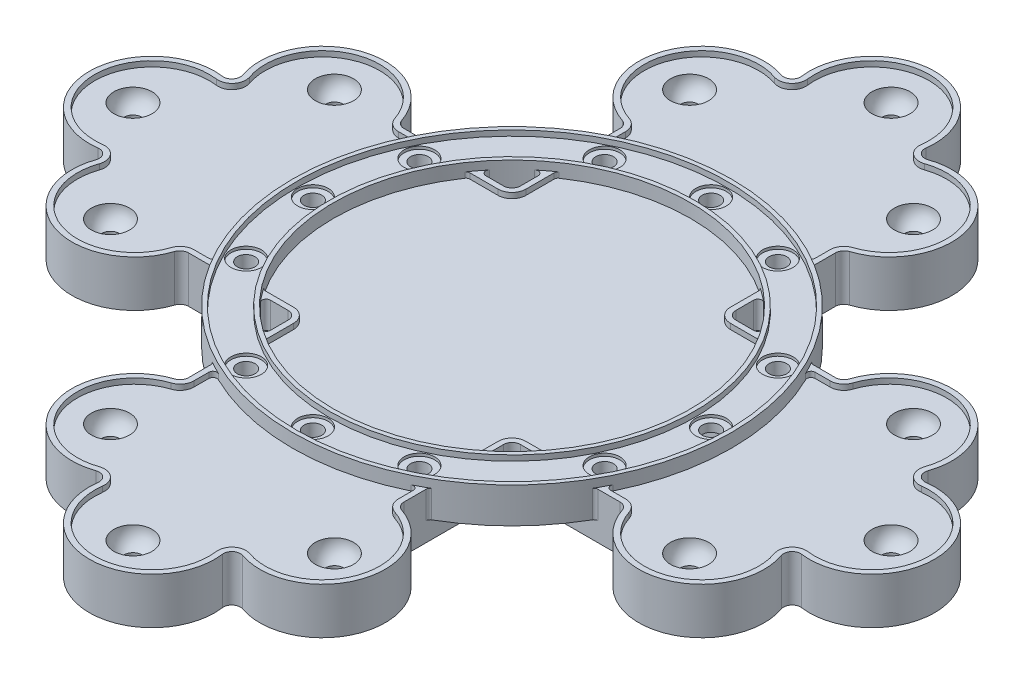
SolidWorks part; units mm, degrees
ref_plane "Front" through (0, 0, 0) normal (0, 0, 1) x (1, 0, 0)
ref_plane "Top" through (0, 0, 0) normal (0, 1, 0) x (1, 0, 0)
ref_plane "Right" through (0, 0, 0) normal (1, 0, 0) x (0, 0, -1)
sketch "Sketch1" plane through (0, 0, 0) normal (0, 1, 0) x (1, 0, 0)
  line L0 (188.3125, 0) -> (-57.7168, 0) construction
  line L1 (39.5, 42.6) -> (39.5, 79.1456)
  line L2 (-39.5, 42.6) -> (-39.5, 79.1456)
  line L3 (-42.6, 39.5) -> (-79.1456, 39.5)
  line L4 (-42.6, -39.5) -> (-79.1456, -39.5)
  line L5 (39.5, 39.5) -> (-39.5, 39.5) construction
  line L6 (0, 39.5) -> (0, 180.1734) construction
  line L7 (-39.5, 39.5) -> (-39.5, -39.5) construction
  line L8 (0, 137) -> (0, -181.6252) construction
  line L9 (-39.5, 0) -> (-180.1734, 0) construction
  line L10 (21, 122.6047) -> (-21, 122.6047) construction
  line L11 (-122.6047, 21) -> (-122.6047, -21) construction
  line L12 (-81.5, 39.5) -> (-81.5, -39.5) construction
  line L13 (39.5, 81.5) -> (-39.5, 81.5) construction
  line L14 (42.6, -39.5) -> (79.1456, -39.5)
  line L15 (42.6, 39.5) -> (79.1456, 39.5)
  line L16 (39.5, -39.5) -> (39.5, 39.5) construction
  line L17 (39.5, 0) -> (180.1734, 0) construction
  line L18 (122.6047, -21) -> (122.6047, 21) construction
  line L19 (81.5, -39.5) -> (81.5, 39.5) construction
  line L20 (-39.5, -42.6) -> (-39.5, -79.1456)
  line L21 (39.5, -42.6) -> (39.5, -79.1456)
  line L22 (-39.5, -39.5) -> (39.5, -39.5) construction
  line L23 (0, -39.5) -> (0, -180.1734) construction
  line L24 (-21, -122.6047) -> (21, -122.6047) construction
  line L25 (-39.5, -81.5) -> (39.5, -81.5) construction
  arc A0 (22.8049, 128.9962) -> (-22.8049, 128.9962) centre (0, 131.9855) ccw
  arc A1 (26.8946, 125.6645) -> (41.6299, 82.0899) centre (34.4327, 103.9349) cw
  arc A2 (-128.9962, 22.8049) -> (-128.9962, -22.8049) centre (-131.9855, 0) ccw
  arc A3 (-125.6645, 26.8946) -> (-82.0899, 41.6299) centre (-103.9349, 34.4327) cw
  arc A4 (-125.6645, -26.8946) -> (-82.0899, -41.6299) centre (-103.9349, -34.4327) ccw
  arc A5 (-26.8946, 125.6645) -> (-41.6299, 82.0899) centre (-34.4327, 103.9349) ccw
  arc A6 (128.9962, -22.8049) -> (128.9962, 22.8049) centre (131.9855, 0) ccw
  arc A7 (125.6645, -26.8946) -> (82.0899, -41.6299) centre (103.9349, -34.4327) cw
  arc A8 (125.6645, 26.8946) -> (82.0899, 41.6299) centre (103.9349, 34.4327) ccw
  arc A9 (-22.8049, -128.9962) -> (22.8049, -128.9962) centre (0, -131.9855) ccw
  arc A10 (-26.8946, -125.6645) -> (-41.6299, -82.0899) centre (-34.4327, -103.9349) cw
  arc A11 (26.8946, -125.6645) -> (41.6299, -82.0899) centre (34.4327, -103.9349) ccw
  arc A12 (-42.6, -39.5) -> (-39.5, -42.6) centre (-42.6, -42.6) cw
  arc A13 (-39.5, -79.1456) -> (-41.6299, -82.0899) centre (-42.6, -79.1456) cw
  arc A14 (-22.8049, -128.9962) -> (-26.8946, -125.6645) centre (-25.8786, -128.5933) ccw
  arc A15 (22.8049, -128.9962) -> (26.8946, -125.6645) centre (25.8786, -128.5933) cw
  arc A16 (39.5, -79.1456) -> (41.6299, -82.0899) centre (42.6, -79.1456) ccw
  arc A17 (42.6, -39.5) -> (39.5, -42.6) centre (42.6, -42.6) ccw
  arc A18 (79.1456, -39.5) -> (82.0899, -41.6299) centre (79.1456, -42.6) cw
  arc A19 (128.9962, -22.8049) -> (125.6645, -26.8946) centre (128.5933, -25.8786) ccw
  arc A20 (128.9962, 22.8049) -> (125.6645, 26.8946) centre (128.5933, 25.8786) cw
  arc A21 (79.1456, 39.5) -> (82.0899, 41.6299) centre (79.1456, 42.6) ccw
  arc A22 (39.5, 42.6) -> (42.6, 39.5) centre (42.6, 42.6) ccw
  arc A23 (39.5, 79.1456) -> (41.6299, 82.0899) centre (42.6, 79.1456) cw
  arc A24 (22.8049, 128.9962) -> (26.8946, 125.6645) centre (25.8786, 128.5933) ccw
  arc A25 (-22.8049, 128.9962) -> (-26.8946, 125.6645) centre (-25.8786, 128.5933) cw
  arc A26 (-39.5, 79.1456) -> (-41.6299, 82.0899) centre (-42.6, 79.1456) ccw
  arc A27 (-42.6, 39.5) -> (-39.5, 42.6) centre (-42.6, 42.6) ccw
  arc A28 (-79.1456, -39.5) -> (-82.0899, -41.6299) centre (-79.1456, -42.6) ccw
  arc A29 (-79.1456, 39.5) -> (-82.0899, 41.6299) centre (-79.1456, 42.6) cw
  arc A30 (-128.9962, -22.8049) -> (-125.6645, -26.8946) centre (-128.5933, -25.8786) cw
  arc A31 (-128.9962, 22.8049) -> (-125.6645, 26.8946) centre (-128.5933, 25.8786) ccw
  point P52 (0, 0)
  dimension "D7" = 3.1
  dimension "D3" = 42
  dimension "D2" = 23
  dimension "D1" = 39.5
  dimension "D4" = 79
  dimension "D5" = 4
  dimension "D6" = 42
extrude "Boss-Extrude1" add sketch "Sketch1" along normal blind 17
ref_plane "Plane1" through (0, 17, 0) normal (0, 1, 0) x (1, 0, 0)
sketch "Sketch8" plane through (0, 17, 0) normal (0, 1, 0) x (1, 0, 0)
  line L244 (42.6, -37.5) -> (79.1456, -37.5)
  line L245 (37.5, -79.1456) -> (37.5, -42.6)
  line L246 (-37.5, -42.6) -> (-37.5, -79.1456)
  line L247 (-79.1456, -37.5) -> (-42.6, -37.5)
  line L248 (79.1456, 37.5) -> (42.6, 37.5)
  line L249 (37.5, 42.6) -> (37.5, 79.1456)
  line L250 (-37.5, 79.1456) -> (-37.5, 42.6)
  line L251 (-42.6, 37.5) -> (-79.1456, 37.5)
  line L252 (42.6, -37.5) -> (79.1456, -37.5)
  line L253 (37.5, -79.1456) -> (37.5, -42.6)
  line L254 (-37.5, -42.6) -> (-37.5, -79.1456)
  line L255 (-79.1456, -37.5) -> (-42.6, -37.5)
  line L256 (79.1456, 37.5) -> (42.6, 37.5)
  line L257 (37.5, 42.6) -> (37.5, 79.1456)
  line L258 (-37.5, 79.1456) -> (-37.5, 42.6)
  line L259 (-42.6, 37.5) -> (-79.1456, 37.5)
  arc A637 (-37.5, 79.1456) -> (-41.0041, 83.9895) centre (-42.6, 79.1456) ccw
  arc A638 (-27.5501, 123.775) -> (-20.8219, 129.2561) centre (-25.8786, 128.5933) ccw
  arc A639 (20.8219, 129.2561) -> (27.5501, 123.775) centre (25.8786, 128.5933) ccw
  arc A640 (41.0041, 83.9895) -> (37.5, 79.1456) centre (42.6, 79.1456) ccw
  arc A641 (79.1456, 37.5) -> (83.9895, 41.0041) centre (79.1456, 42.6) ccw
  arc A642 (123.775, 27.5501) -> (83.9895, 41.0041) centre (103.9349, 34.4327) ccw
  arc A643 (123.775, 27.5501) -> (129.2561, 20.8219) centre (128.5933, 25.8786) ccw
  arc A644 (129.2561, -20.8219) -> (129.2561, 20.8219) centre (131.9855, 0) ccw
  arc A645 (129.2561, -20.8219) -> (123.775, -27.5501) centre (128.5933, -25.8786) ccw
  arc A646 (83.9895, -41.0041) -> (123.775, -27.5501) centre (103.9349, -34.4327) ccw
  arc A647 (83.9895, -41.0041) -> (79.1456, -37.5) centre (79.1456, -42.6) ccw
  arc A648 (42.6, -37.5) -> (37.5, -42.6) centre (42.6, -42.6) ccw
  arc A649 (37.5, -79.1456) -> (41.0041, -83.9895) centre (42.6, -79.1456) ccw
  arc A650 (27.5501, -123.775) -> (41.0041, -83.9895) centre (34.4327, -103.9349) ccw
  arc A651 (27.5501, -123.775) -> (20.8219, -129.2561) centre (25.8786, -128.5933) ccw
  arc A652 (-20.8219, -129.2561) -> (20.8219, -129.2561) centre (0, -131.9855) ccw
  arc A653 (-20.8219, -129.2561) -> (-27.5501, -123.775) centre (-25.8786, -128.5933) ccw
  arc A654 (-41.0041, -83.9895) -> (-27.5501, -123.775) centre (-34.4327, -103.9349) ccw
  arc A655 (-41.0041, -83.9895) -> (-37.5, -79.1456) centre (-42.6, -79.1456) ccw
  arc A656 (-37.5, -42.6) -> (-42.6, -37.5) centre (-42.6, -42.6) ccw
  arc A657 (-79.1456, -37.5) -> (-83.9895, -41.0041) centre (-79.1456, -42.6) ccw
  arc A658 (-123.775, -27.5501) -> (-83.9895, -41.0041) centre (-103.9349, -34.4327) ccw
  arc A659 (-123.775, -27.5501) -> (-129.2561, -20.8219) centre (-128.5933, -25.8786) ccw
  arc A660 (-129.2561, 20.8219) -> (-129.2561, -20.8219) centre (-131.9855, 0) ccw
  arc A661 (-129.2561, 20.8219) -> (-123.775, 27.5501) centre (-128.5933, 25.8786) ccw
  arc A662 (-83.9895, 41.0041) -> (-79.1456, 37.5) centre (-79.1456, 42.6) ccw
  arc A663 (-83.9895, 41.0041) -> (-123.775, 27.5501) centre (-103.9349, 34.4327) ccw
  arc A664 (37.5, 42.6) -> (42.6, 37.5) centre (42.6, 42.6) ccw
  arc A665 (-42.6, 37.5) -> (-37.5, 42.6) centre (-42.6, 42.6) ccw
  arc A666 (41.0041, 83.9895) -> (27.5501, 123.775) centre (34.4327, 103.9349) ccw
  arc A667 (20.8219, 129.2561) -> (-20.8219, 129.2561) centre (0, 131.9855) ccw
  arc A668 (-27.5501, 123.775) -> (-41.0041, 83.9895) centre (-34.4327, 103.9349) ccw
  arc A669 (-37.5, 79.1456) -> (-41.0041, 83.9895) centre (-42.6, 79.1456) ccw
  arc A670 (-27.5501, 123.775) -> (-20.8219, 129.2561) centre (-25.8786, 128.5933) ccw
  arc A671 (20.8219, 129.2561) -> (27.5501, 123.775) centre (25.8786, 128.5933) ccw
  arc A672 (41.0041, 83.9895) -> (37.5, 79.1456) centre (42.6, 79.1456) ccw
  arc A673 (79.1456, 37.5) -> (83.9895, 41.0041) centre (79.1456, 42.6) ccw
  arc A674 (123.775, 27.5501) -> (83.9895, 41.0041) centre (103.9349, 34.4327) ccw
  arc A675 (123.775, 27.5501) -> (129.2561, 20.8219) centre (128.5933, 25.8786) ccw
  arc A676 (129.2561, -20.8219) -> (129.2561, 20.8219) centre (131.9855, 0) ccw
  arc A677 (129.2561, -20.8219) -> (123.775, -27.5501) centre (128.5933, -25.8786) ccw
  arc A678 (83.9895, -41.0041) -> (123.775, -27.5501) centre (103.9349, -34.4327) ccw
  arc A679 (83.9895, -41.0041) -> (79.1456, -37.5) centre (79.1456, -42.6) ccw
  arc A680 (42.6, -37.5) -> (37.5, -42.6) centre (42.6, -42.6) ccw
  arc A681 (37.5, -79.1456) -> (41.0041, -83.9895) centre (42.6, -79.1456) ccw
  arc A682 (27.5501, -123.775) -> (41.0041, -83.9895) centre (34.4327, -103.9349) ccw
  arc A683 (27.5501, -123.775) -> (20.8219, -129.2561) centre (25.8786, -128.5933) ccw
  arc A684 (-20.8219, -129.2561) -> (20.8219, -129.2561) centre (0, -131.9855) ccw
  arc A685 (-20.8219, -129.2561) -> (-27.5501, -123.775) centre (-25.8786, -128.5933) ccw
  arc A686 (-41.0041, -83.9895) -> (-27.5501, -123.775) centre (-34.4327, -103.9349) ccw
  arc A687 (-41.0041, -83.9895) -> (-37.5, -79.1456) centre (-42.6, -79.1456) ccw
  arc A688 (-37.5, -42.6) -> (-42.6, -37.5) centre (-42.6, -42.6) ccw
  arc A689 (-79.1456, -37.5) -> (-83.9895, -41.0041) centre (-79.1456, -42.6) ccw
  arc A690 (-123.775, -27.5501) -> (-83.9895, -41.0041) centre (-103.9349, -34.4327) ccw
  arc A691 (-123.775, -27.5501) -> (-129.2561, -20.8219) centre (-128.5933, -25.8786) ccw
  arc A692 (-129.2561, 20.8219) -> (-129.2561, -20.8219) centre (-131.9855, 0) ccw
  arc A693 (-129.2561, 20.8219) -> (-123.775, 27.5501) centre (-128.5933, 25.8786) ccw
  arc A694 (-83.9895, 41.0041) -> (-79.1456, 37.5) centre (-79.1456, 42.6) ccw
  arc A695 (-83.9895, 41.0041) -> (-123.775, 27.5501) centre (-103.9349, 34.4327) ccw
  arc A696 (37.5, 42.6) -> (42.6, 37.5) centre (42.6, 42.6) ccw
  arc A697 (-42.6, 37.5) -> (-37.5, 42.6) centre (-42.6, 42.6) ccw
  arc A698 (41.0041, 83.9895) -> (27.5501, 123.775) centre (34.4327, 103.9349) ccw
  arc A699 (20.8219, 129.2561) -> (-20.8219, 129.2561) centre (0, 131.9855) ccw
  arc A700 (-27.5501, 123.775) -> (-41.0041, 83.9895) centre (-34.4327, 103.9349) ccw
  dimension "D1" = 2
extrude "Cut-Extrude1" cut sketch "Sketch8" against normal blind 2
sketch "Sketch9" plane through (0, 17, 0) normal (0, 1, 0) x (1, 0, 0)
  circle A0 centre (0, 0) radius 65.5
  circle A1 centre (0, 0) radius 80.5
  dimension "D1" = 131
  dimension "D2" = 161
extrude "Boss-Extrude3" add sketch "Sketch9" along normal blind 3 and the other way blind 10
ref_plane "Plane2" through (0, 20, 0) normal (0, 1, 0) x (1, 0, 0)
sketch "Sketch11" plane through (0, 20, 0) normal (0, 1, 0) x (1, 0, 0)
  circle A9 centre (0, 0) radius 79
  circle A10 centre (0, 0) radius 79
  circle A12 centre (0, 0) radius 67
  circle A13 centre (0, 0) radius 67
  dimension "D1" = 1.5
  dimension "D2" = 1.5
extrude "Cut-Extrude2" cut sketch "Sketch11" against normal blind 2
ref_plane "Plane3" through (0, 0, 0) normal (0, -1, 0) x (-1, 0, 0)
sketch "Sketch12" plane through (0, 0, 0) normal (0, -1, 0) x (-1, 0, 0)
  line L0 (-49.0448, 35.71) -> (-6.2448, 35.71)
  line L1 (-3.1448, 38.81) -> (-3.1448, 61.81)
  line L2 (-3.1448, 61.81) -> (18.8552, 61.81)
  line L3 (18.8552, 61.81) -> (18.8552, 38.81)
  line L4 (21.9552, 35.71) -> (45.7552, 35.71)
  line L5 (48.8552, 32.61) -> (48.8552, 0.81)
  line L6 (51.9552, -2.29) -> (74.9552, -2.29)
  line L7 (74.9552, -2.29) -> (74.9552, -25.29)
  line L8 (74.9552, -25.29) -> (51.9552, -25.29)
  line L9 (48.8552, -28.39) -> (48.8552, -33.19)
  line L10 (45.7552, -36.29) -> (24.9552, -36.29)
  line L11 (21.8552, -39.39) -> (21.8552, -62.39)
  line L12 (21.8552, -62.39) -> (-0.1448, -62.39)
  line L13 (-0.1448, -62.39) -> (-0.1448, -39.39)
  line L14 (-3.2448, -36.29) -> (-49.0448, -36.29)
  line L15 (-52.1448, -33.19) -> (-52.1448, -11.39)
  line L16 (-55.2448, -8.29) -> (-78.2448, -8.29)
  line L17 (-78.2448, -8.29) -> (-78.2448, 13.71)
  line L18 (-78.2448, 13.71) -> (-55.2448, 13.71)
  line L19 (-52.1448, 16.81) -> (-52.1448, 32.61)
  arc A0 (-6.2448, 35.71) -> (-3.1448, 38.81) centre (-6.2448, 38.81) ccw
  arc A1 (18.8552, 38.81) -> (21.9552, 35.71) centre (21.9552, 38.81) ccw
  arc A2 (45.7552, 35.71) -> (48.8552, 32.61) centre (45.7552, 32.61) cw
  arc A3 (48.8552, 0.81) -> (51.9552, -2.29) centre (51.9552, 0.81) ccw
  arc A4 (51.9552, -25.29) -> (48.8552, -28.39) centre (51.9552, -28.39) ccw
  arc A5 (48.8552, -33.19) -> (45.7552, -36.29) centre (45.7552, -33.19) cw
  arc A6 (24.9552, -36.29) -> (21.8552, -39.39) centre (24.9552, -39.39) ccw
  arc A7 (-0.1448, -39.39) -> (-3.2448, -36.29) centre (-3.2448, -39.39) ccw
  arc A8 (-49.0448, -36.29) -> (-52.1448, -33.19) centre (-49.0448, -33.19) cw
  arc A9 (-52.1448, -11.39) -> (-55.2448, -8.29) centre (-55.2448, -11.39) ccw
  arc A10 (-55.2448, 13.71) -> (-52.1448, 16.81) centre (-55.2448, 16.81) ccw
  arc A11 (-49.0448, 35.71) -> (-52.1448, 32.61) centre (-49.0448, 32.61) ccw
  point P22 (-3.1448, 35.71)
  point P25 (18.8552, 35.71)
  point P28 (48.8552, 35.71)
  point P31 (48.8552, -2.29)
  point P34 (48.8552, -25.29)
  point P37 (48.8552, -36.29)
  point P40 (21.8552, -36.29)
  point P43 (-0.1448, -36.29)
  point P46 (-52.1448, -36.29)
  point P49 (-52.1448, -8.29)
  point P52 (-52.1448, 13.71)
  point P55 (-52.1448, 35.71)
  dimension "D11" = 3.1
  dimension "D1" = 72
  dimension "D2" = 101
  dimension "D3" = 30
  dimension "D4" = 22
  dimension "D5" = 22
  dimension "D6" = 22
  dimension "D7" = 52
  dimension "D8" = 22
  dimension "D9" = 11
  dimension "D10" = 23
  dimension "D12" = 23
  dimension "D13" = 23
  dimension "D14" = 23
  dimension "D15" = 23
extrude "Cut-Extrude3" cut sketch "Sketch12" against normal blind 14
ref_plane "Plane4" through (0, 18, 0) normal (0, 1, 0) x (1, 0, 0)
sketch "Sketch13" plane through (0, 18, 0) normal (0, 1, 0) x (1, 0, 0)
  line L0 (0, 109.8367) -> (0, 39.5) construction
  line L1 (0, 39.5) -> (0, 180.1734) construction
  circle A0 centre (0, 0) radius 73 construction
  circle A1 centre (0, 73) radius 3.25
  circle A2 centre (-31.7669, 65.7257) radius 3.25
  circle A3 centre (31.7669, 65.7257) radius 3.25
  circle A4 centre (65.7257, 31.7669) radius 3.25
  circle A5 centre (73, 0) radius 3.25
  circle A6 centre (65.7257, -31.7669) radius 3.25
  circle A7 centre (31.7669, -65.7257) radius 3.25
  circle A8 centre (0, -73) radius 3.25
  circle A9 centre (-31.7669, -65.7257) radius 3.25
  circle A10 centre (-65.7257, -31.7669) radius 3.25
  circle A11 centre (-73, 0) radius 3.25
  circle A12 centre (-65.7257, 31.7669) radius 3.25
  point P35 (0, 0)
  dimension "D1" = 146
  dimension "D2" = 6.5
  dimension "D3" = 6.5
  dimension "D4" = 4
extrude "Cut-Extrude4" cut sketch "Sketch13" against normal through all
sketch "Sketch14" plane through (0, 18, 0) normal (0, 1, 0) x (1, 0, 0)
  line L0 (0, 39.5) -> (0, 180.1734) construction
  line L1 (0, 99.6735) -> (0, 45.2038) construction
  circle A0 centre (0, 0) radius 73 construction
  circle A1 centre (0, 73) radius 5.6
  circle A2 centre (-31.7669, 65.7257) radius 5.6
  circle A3 centre (31.7669, 65.7257) radius 5.6
  circle A4 centre (65.7257, 31.7669) radius 5.6
  circle A5 centre (73, 0) radius 5.6
  circle A6 centre (65.7257, -31.7669) radius 5.6
  circle A7 centre (31.7669, -65.7257) radius 5.6
  circle A8 centre (0, -73) radius 5.6
  circle A9 centre (-31.7669, -65.7257) radius 5.6
  circle A10 centre (-65.7257, -31.7669) radius 5.6
  circle A11 centre (-73, 0) radius 5.6
  circle A12 centre (-65.7257, 31.7669) radius 5.6
  point P35 (0, 0)
  dimension "D1" = 146
  dimension "D2" = 11.2
  dimension "D3" = 11.2
  dimension "D4" = 4
extrude "Cut-Extrude5" cut sketch "Sketch14" against normal blind 1
sketch "Sketch15" plane through (0, 17, 0) normal (0, 1, 0) x (1, 0, 0)
  line L0 (0, 131.9855) -> (0, 152.9855) construction
  line L2 (-34.4327, 103.9349) -> (-54.326, 110.6621) construction
  circle A0 centre (-41.0638, 106.1773) radius 7 construction
  arc A1 (-27.5501, 123.775) -> (-41.0041, 83.9895) centre (-34.4327, 103.9349) ccw construction
  circle A2 centre (-41.0638, 106.1773) radius 3.25
  arc A3 (20.8219, 129.2561) -> (-20.8219, 129.2561) centre (0, 131.9855) ccw construction
  circle A4 centre (0, 138.9855) radius 7 construction
  circle A5 centre (0, 138.9855) radius 3.25
  circle A6 centre (41.0638, 106.1773) radius 3.25
  circle A7 centre (106.1773, 41.0638) radius 3.25
  circle A8 centre (138.9855, 0) radius 3.25
  circle A9 centre (106.1773, -41.0638) radius 3.25
  circle A10 centre (41.0638, -106.1773) radius 3.25
  circle A11 centre (0, -138.9855) radius 3.25
  circle A12 centre (-41.0638, -106.1773) radius 3.25
  circle A13 centre (-106.1773, -41.0638) radius 3.25
  circle A14 centre (-138.9855, 0) radius 3.25
  circle A15 centre (-106.1773, 41.0638) radius 3.25
  point P41 (0, 0)
  dimension "D1" = 14
  dimension "D2" = 6.5
  dimension "D3" = 14
  dimension "D4" = 6.5
  dimension "D5" = 4
extrude "Cut-Extrude6" cut sketch "Sketch15" against normal through all
sketch "Sketch16" plane through (0, 0, 0) normal (1, 0, 0) x (0, 0, -1)
  line L0 (131.9855, 15) -> (138.9855, 15)
  line L1 (138.9855, 15) -> (138.9855, 8)
  line L4 (135.7355, 15) -> (142.2355, 15) construction
  line L5 (142.2355, 15) -> (135.7355, 15) construction
  line L6 (152.9855, 15) -> (129.2561, 15) construction
  arc A0 (138.9855, 8) -> (131.9855, 15) centre (138.9855, 15) cw
  dimension "D1" = 7
revolve "Cut-Revolve1" cut sketch "Sketch16" angle 360 about L1
ref_axis "Axis1" through (41.0638, 0, -106.1773) along (0, 1, 0)
ref_plane "Plane5" through (41.0638, 0, 0) normal (1, 0, 0) x (0, 0, -1)
sketch "Sketch18" plane through (41.0638, 0, 0) normal (1, 0, 0) x (0, 0, -1)
  line L0 (99.1773, 15) -> (106.1773, 15)
  line L1 (106.1773, 15) -> (106.1773, 8)
  line L3 (102.9273, 15) -> (109.4273, 15) construction
  arc A0 (99.1773, 15) -> (106.1773, 8) centre (106.1773, 15) ccw
  dimension "D1" = 7
revolve "Cut-Revolve3" cut sketch "Sketch18" angle 360 about L1
ref_axis "Axis2" through (-41.0638, 0, -106.1773) along (0, 1, 0)
mirror "Mirror1" about plane through (0, 0, 0) normal (1, 0, 0) of "Cut-Revolve3"
ref_axis "Axis3" through (0, 0, 0) along (0, 1, 0)
pattern_circular "CirPattern1" count 4 over 360 about axis through (0, 0, 0) along (0, 1, 0) of "Cut-Revolve1", "Cut-Revolve3", "Mirror1"
sketch "Sketch19" plane through (0, 0, 0) normal (0, -1, 0) x (-1, 0, 0)
  line L0 (-78.2448, 13.71) -> (-87.017, 13.71)
  line L1 (-90.117, 16.81) -> (-90.117, 25.8454)
  line L2 (-87.017, 28.9454) -> (-65.921, 28.9454)
  line L3 (-65.921, 28.9454) -> (-65.921, 32.6006)
  line L4 (-65.921, 32.6006) -> (-101.2665, 32.6006)
  line L5 (-104.3665, 35.7006) -> (-104.3665, 41.0638)
  line L6 (-104.3665, 41.0638) -> (-107.8155, 41.0638)
  line L7 (-107.8155, 41.0638) -> (-107.8155, 13.71)
  line L8 (-107.8155, 13.71) -> (-107.8155, 5.4684)
  line L9 (-110.9155, 2.3684) -> (-137.9358, 2.3684)
  line L10 (-137.9358, 2.3684) -> (-137.9358, -1.5741)
  line L11 (-137.9358, -1.5741) -> (-110.9155, -1.5741)
  line L12 (-107.8155, -4.6741) -> (-107.8155, -40.3886)
  line L13 (-107.8155, -40.3886) -> (-104.3665, -40.3886)
  line L14 (-104.3665, -40.3886) -> (-104.3665, -37.5327)
  line L15 (-101.2665, -34.4327) -> (-65.921, -34.4327)
  line L16 (-65.921, -34.4327) -> (-65.921, -29.8338)
  line L17 (-65.921, -29.8338) -> (-87.017, -29.8338)
  line L18 (-90.117, -26.7338) -> (-90.117, -11.4)
  line L19 (-87.0206, -8.3) -> (-78.2448, -8.29)
  line L20 (-78.2448, -8.29) -> (-78.2448, 13.71)
  line L22 (-3.1448, 61.81) -> (-31.7669, 62.4757)
  line L23 (-31.7669, 62.4757) -> (-31.7669, 68.9757)
  line L24 (-31.7669, 68.9757) -> (-11.0716, 68.9757)
  line L25 (-7.9716, 72.0757) -> (-7.9716, 99.676)
  line L26 (-11.0559, 102.776) -> (-41.0638, 102.9273)
  line L27 (-41.0638, 102.9273) -> (-41.0638, 109.4273)
  line L28 (-41.0638, 9.9) -> (-41.0638, -9.9) construction
  line L29 (-41.0638, 109.4273) -> (-5.8699, 109.4273)
  line L30 (-2.7699, 112.5273) -> (-2.7699, 138.9855)
  line L31 (-2.7699, 138.9855) -> (3.25, 138.9855)
  line L32 (3.25, 138.9855) -> (3.25, 112.5273)
  line L33 (6.35, 109.4273) -> (41.0638, 109.4273)
  line L34 (41.0638, 109.4273) -> (41.0638, 102.9273)
  line L35 (41.0638, 102.9273) -> (6.2493, 102.9273)
  line L36 (3.1493, 99.8273) -> (3.1493, 72.0757)
  line L37 (6.2493, 68.9757) -> (31.7669, 68.9757)
  line L38 (31.7669, 68.9757) -> (31.7669, 62.4757)
  line L39 (31.7669, 62.4757) -> (18.8552, 61.81)
  line L40 (18.8552, 61.81) -> (-3.1448, 61.81)
  line L41 (65.7257, -29.8338) -> (71.8552, -29.8338)
  line L42 (74.9552, -26.7338) -> (74.9552, -25.29)
  line L43 (-31.7669, -62.4757) -> (-0.1448, -62.4757)
  line L44 (65.7257, -29.8338) -> (65.7257, -35.0169)
  line L45 (65.7257, -35.0169) -> (100.8349, -35.0169)
  line L46 (103.9349, -38.1169) -> (103.9349, -41.0638)
  line L47 (103.9349, -41.0638) -> (109.4273, -41.0638)
  line L48 (109.4273, -41.0638) -> (109.4273, -5.6961)
  line L49 (112.5273, -2.5961) -> (139.1518, -2.5961)
  line L50 (139.1518, -2.5961) -> (138.9855, 3.25)
  line L51 (138.9855, 3.25) -> (112.5273, 3.25)
  line L52 (109.4273, 6.35) -> (109.4273, 41.0638)
  line L53 (109.4273, 41.0638) -> (102.9273, 41.0638)
  line L54 (102.9273, 41.0638) -> (102.9273, 37.6246)
  line L55 (99.8273, 34.5246) -> (65.7257, 34.5246)
  line L56 (65.7257, 34.5246) -> (65.7257, 28.9454)
  line L57 (65.7257, 28.9454) -> (83.7971, 28.9454)
  line L58 (86.8971, 25.8454) -> (86.8971, 6.2631)
  line L59 (83.8852, 3.1643) -> (74.4737, 2.8966)
  line L61 (74.4737, 2.8966) -> (74.9552, -25.29)
  line L62 (31.7669, -62.4757) -> (31.7669, -68.9757)
  line L63 (31.7669, -68.9757) -> (24.9552, -68.9757)
  line L64 (21.8552, -72.0757) -> (21.8552, -99.8273)
  line L65 (24.9552, -102.9273) -> (41.0638, -102.9273)
  line L66 (41.0638, -102.9273) -> (41.0638, -109.4273)
  line L67 (41.0638, -109.4273) -> (6.35, -109.4273)
  line L68 (3.25, -112.5273) -> (3.25, -138.9855)
  line L69 (3.25, -138.9855) -> (-3.25, -138.9855)
  line L70 (-3.25, -138.9855) -> (-3.25, -112.5273)
  line L71 (-6.35, -109.4273) -> (-41.0638, -109.4273)
  line L72 (-41.0638, -109.4273) -> (-41.0638, -102.9273)
  line L73 (-41.0638, -102.9273) -> (-6.35, -102.9273)
  line L74 (-3.25, -99.8273) -> (-3.25, -72.0757)
  line L75 (-6.35, -68.9757) -> (-31.7669, -68.9757)
  line L76 (-31.7669, -68.9757) -> (-31.7669, -62.4757)
  line L77 (-0.1448, -62.4757) -> (-0.1448, -62.39)
  line L78 (-0.1448, -62.39) -> (21.8552, -62.39)
  line L79 (21.8552, -62.39) -> (21.8552, -62.4757)
  line L80 (21.8552, -62.4757) -> (31.7669, -62.4757)
  arc A0 (-87.017, 13.71) -> (-90.117, 16.81) centre (-87.017, 16.81) cw
  arc A1 (-90.117, -11.4) -> (-87.0206, -8.3) centre (-87.017, -11.4) cw
  arc A2 (-87.017, -29.8338) -> (-90.117, -26.7338) centre (-87.017, -26.7338) cw
  arc A3 (-104.3665, -37.5327) -> (-101.2665, -34.4327) centre (-101.2665, -37.5327) cw
  arc A4 (-110.9155, -1.5741) -> (-107.8155, -4.6741) centre (-110.9155, -4.6741) cw
  arc A5 (-107.8155, 5.4684) -> (-110.9155, 2.3684) centre (-110.9155, 5.4684) cw
  arc A6 (-101.2665, 32.6006) -> (-104.3665, 35.7006) centre (-101.2665, 35.7006) cw
  arc A7 (-90.117, 25.8454) -> (-87.017, 28.9454) centre (-87.017, 25.8454) cw
  circle A8 centre (-31.7669, 65.7257) radius 3.25 construction
  circle A9 centre (-41.0638, 106.1773) radius 3.25 construction
  circle A10 centre (0, 138.9855) radius 3.25 construction
  circle A11 centre (41.0638, 106.1773) radius 3.25 construction
  circle A12 centre (31.7669, 65.7257) radius 3.25 construction
  arc A13 (3.1493, 72.0757) -> (6.2493, 68.9757) centre (6.2493, 72.0757) ccw
  arc A14 (6.2493, 102.9273) -> (3.1493, 99.8273) centre (6.2493, 99.8273) ccw
  arc A15 (3.25, 112.5273) -> (6.35, 109.4273) centre (6.35, 112.5273) ccw
  arc A16 (-5.8699, 109.4273) -> (-2.7699, 112.5273) centre (-5.8699, 112.5273) ccw
  arc A18 (-7.9716, 99.676) -> (-11.0559, 102.776) centre (-11.0716, 99.676) ccw
  arc A19 (-11.0716, 68.9757) -> (-7.9716, 72.0757) centre (-11.0716, 72.0757) ccw
  circle A20 centre (65.7257, -31.7669) radius 3.25 construction
  circle A21 centre (106.1773, -41.0638) radius 3.25 construction
  circle A22 centre (138.9855, 0) radius 3.25 construction
  circle A23 centre (106.1773, 41.0638) radius 3.25 construction
  arc A24 (74.9552, -2.5961) -> (70.6939, -2.29) centre (73, 0) ccw construction
  arc A25 (86.8971, 6.2631) -> (83.8852, 3.1643) centre (83.7971, 6.2631) cw
  arc A26 (83.7971, 28.9454) -> (86.8971, 25.8454) centre (83.7971, 25.8454) cw
  arc A27 (102.9273, 37.6246) -> (99.8273, 34.5246) centre (99.8273, 37.6246) cw
  arc A28 (112.5273, 3.25) -> (109.4273, 6.35) centre (112.5273, 6.35) cw
  arc A31 (109.4273, -5.6961) -> (112.5273, -2.5961) centre (112.5273, -5.6961) cw
  arc A32 (100.8349, -35.0169) -> (103.9349, -38.1169) centre (100.8349, -38.1169) cw
  arc A33 (71.8552, -29.8338) -> (74.9552, -26.7338) centre (71.8552, -26.7338) ccw
  circle A34 centre (31.7669, -65.7257) radius 3.25 construction
  circle A35 centre (41.0638, -106.1773) radius 3.25 construction
  circle A36 centre (0, -138.9855) radius 3.25 construction
  circle A37 centre (-41.0638, -106.1773) radius 3.25 construction
  circle A38 centre (-31.7669, -65.7257) radius 3.25 construction
  arc A39 (-3.25, -112.5273) -> (-6.35, -109.4273) centre (-6.35, -112.5273) ccw
  arc A40 (6.35, -109.4273) -> (3.25, -112.5273) centre (6.35, -112.5273) ccw
  arc A41 (21.8552, -99.8273) -> (24.9552, -102.9273) centre (24.9552, -99.8273) ccw
  arc A42 (-6.35, -102.9273) -> (-3.25, -99.8273) centre (-6.35, -99.8273) ccw
  arc A43 (24.9552, -68.9757) -> (21.8552, -72.0757) centre (24.9552, -72.0757) ccw
  arc A44 (-3.25, -72.0757) -> (-6.35, -68.9757) centre (-6.35, -72.0757) ccw
  circle A46 centre (0, -73) radius 3.25 construction
  dimension "D1" = 3.1
  dimension "D2" = 3.1
  dimension "D3" = 3.1
  dimension "D4" = 3.1
  dimension "D5" = 3.1
  dimension "D6" = 3.1
  dimension "D7" = 3.1
  dimension "D8" = 3.1
  dimension "D9" = 3.1
  dimension "D10" = 3.1
  dimension "D11" = 3.1
extrude "Cut-Extrude7" cut sketch "Sketch19" against normal blind 5
fillet "Fillet1" radius 1.55 1 edges at (37.5, 16, -71.232)
fillet "Fillet2" radius 1.5 7 edges at (-37.5, 16, 71.232) (37.5, 16, 71.232) (-71.232, 16, 37.5) (-71.232, 16, -37.5) (-37.5, 16, -71.232) (71.232, 16, 37.5) (71.232, 16, -37.5)
fillet "Fillet3" radius 1.5 8 edges at (53.7029, 16, -37.5) (37.5, 16, -53.7029) (-37.5, 16, -53.7029) (-53.7029, 16, -37.5) (-53.7029, 16, 37.5) (-37.5, 16, 53.7029) (53.7029, 16, 37.5) (37.5, 16, 53.7029)
fillet "Fillet4" radius 1.5 8 edges at (39.5, 12, 52.2494) (52.2494, 12, 39.5) (52.2494, 12, -39.5) (39.5, 12, -52.2494) (-39.5, 12, -52.2494) (-52.2494, 12, -39.5) (-39.5, 12, 52.2494) (-52.2494, 12, 39.5)
fillet "Fillet5" radius 1.5 8 edges at (39.5, 12, -70.1427) (70.1427, 12, -39.5) (70.1427, 12, 39.5) (39.5, 12, 70.1427) (-39.5, 12, 70.1427) (-70.1427, 12, 39.5) (-39.5, 12, -70.1427) (-70.1427, 12, -39.5)
